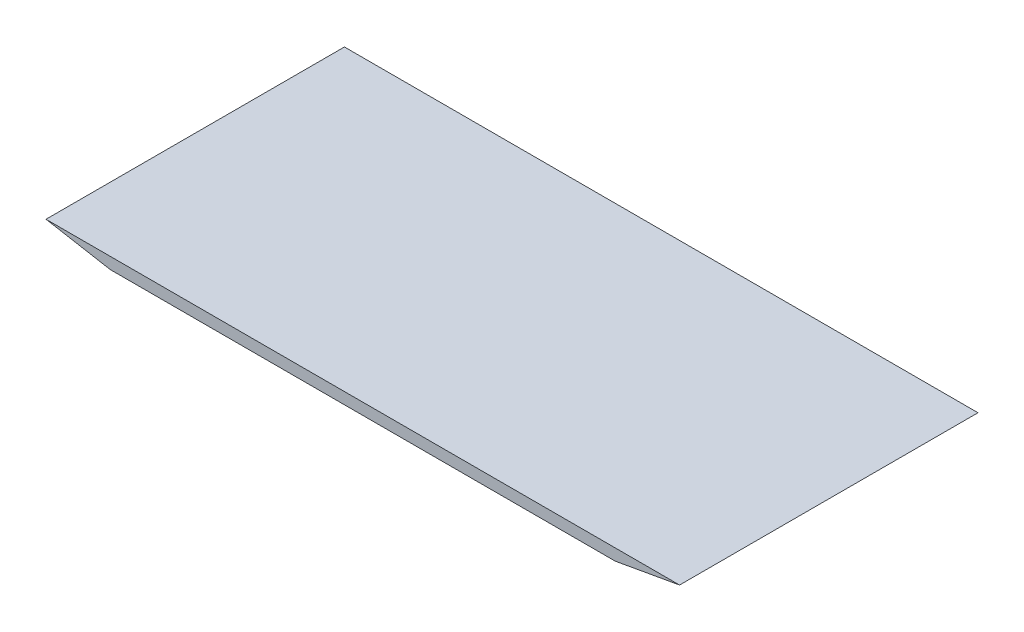
SolidWorks part; units mm, degrees
ref_plane "Front Plane" through (0, 0, 0) normal (0, 0, 1) x (1, 0, 0)
ref_plane "Top Plane" through (0, 0, 0) normal (0, 1, 0) x (1, 0, 0)
ref_plane "Right Plane" through (0, 0, 0) normal (1, 0, 0) x (0, 0, -1)
sketch "Sketch1" plane through (0, 0, 0) normal (0, 0, 1) x (1, 0, 0)
  line L0 (0, 0) -> (276, 0)
  line L2 (248, -5) -> (28, -5)
  line L3 (28, -5) -> (0, 0)
  line L4 (276, 0) -> (248, -5)
  dimension "D1" = 5
  dimension "D2" = 28
  dimension "D3" = 28
  dimension "D4" = 220
extrude "Boss-Extrude1" add sketch "Sketch1" along normal blind 130 contours L3 L0 L4 L2
